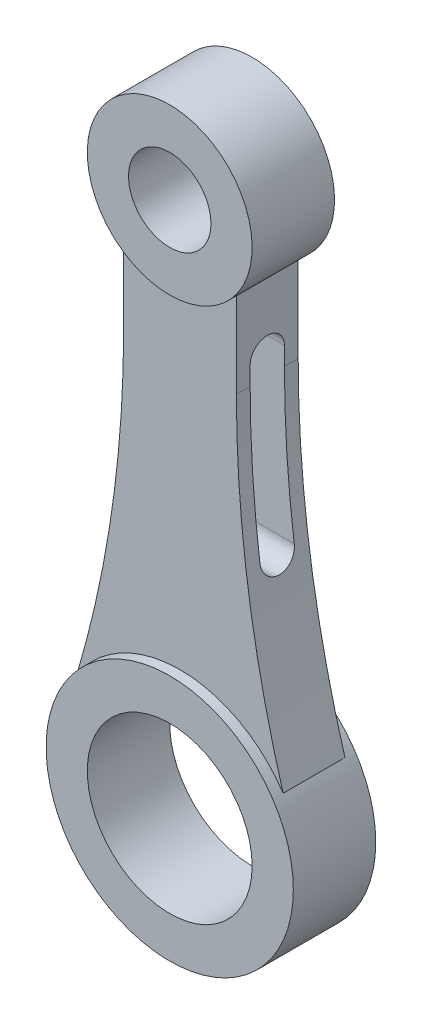
SolidWorks part; units mm, degrees
ref_plane "Front Plane" through (0, 0, 0) normal (0, 0, 1) x (1, 0, 0)
ref_plane "Top Plane" through (0, 0, 0) normal (0, 1, 0) x (1, 0, 0)
ref_plane "Right Plane" through (0, 0, 0) normal (1, 0, 0) x (0, 0, -1)
sketch "Sketch1" plane through (0, 0, 0) normal (0, 0, 1) x (1, 0, 0)
  line L0 (-1043.1714, 0) -> (51115.3996, 0) construction
  line L1 (0, -1043.1714) -> (0, 51115.3996) construction
  line L2 (-13.3674, 36.1872) -> (-13.6805, 36.4746)
  line L3 (-13.6805, 36.4746) -> (-13.6805, 15.8202)
  line L4 (13.6805, 36.4746) -> (13.6805, 15.8202)
  circle A0 centre (0, -78.9362) radius 30
  circle A1 centre (0, -78.9362) radius 20
  circle A2 centre (0, 51.0638) radius 20
  circle A3 centre (0, 51.0638) radius 10
  arc A4 (-13.6805, 15.8202) -> (-25.0234, -62.3884) centre (-288.972, 15.8202) cw
  arc A5 (13.6805, 15.8202) -> (25.0234, -62.3884) centre (288.972, 15.8202) ccw
  dimension "D1" = 40
  dimension "D2" = 20
  dimension "D3" = 60
  dimension "D4" = 40
  dimension "D5" = 130
extrude "Boss-Extrude1" add sketch "Sketch1" along normal mid plane 20 contours A0 A1 | L2 A2 A3 region at (-13.1414, 36.7477, 0) region at (0, -49.7847, 0)
extrude "Boss-Extrude4" add sketch "Sketch1<4>" along normal mid plane 15 separate body contours A5 L4 A2 L3 A4 A0 region at (0, -13.5318, 0)
sketch "Sketch1<4>" plane through (0, 0, 0) normal (0, 0, 1) x (1, 0, 0) same geometry as "Sketch1"
sketch "Sketch2" plane through (0, 0, 0) normal (1, 0, 0) x (0, 0, -1)
  line L0 (0, 20.2587) -> (0, -20.2587) construction
  line L1 (4.1567, 20.2587) -> (4.1567, -20.2587)
  line L2 (-4.1567, 20.2587) -> (-4.1567, -20.2587)
  arc A0 (4.1567, 20.2587) -> (-4.1567, 20.2587) centre (0, 20.2587) ccw
  arc A1 (-4.1567, -20.2587) -> (4.1567, -20.2587) centre (0, -20.2587) ccw
  point P2 (0, 0)
extrude "Cut-Extrude1" cut sketch "Sketch2" against normal through all both and the other way through all from offset 3
sketch "Sketch3" plane through (0, 0, 0) normal (0, 0, 1) x (1, 0, 0)
  line L0 (0, 0) -> (0, -18.5506) construction
  line L1 (6.7031, 0) -> (6.7031, -18.5506)
  line L2 (-6.7031, 0) -> (-6.7031, -18.5506)
  arc A0 (6.7031, 0) -> (-6.7031, 0) centre (0, 0) ccw
  arc A1 (-6.7031, -18.5506) -> (6.7031, -18.5506) centre (0, -18.5506) ccw
  point P3 (0, -9.2753)
extrude "Cut-Extrude2" cut sketch "Sketch3" against normal mid plane 1 from offset 5 offset against normal yes
